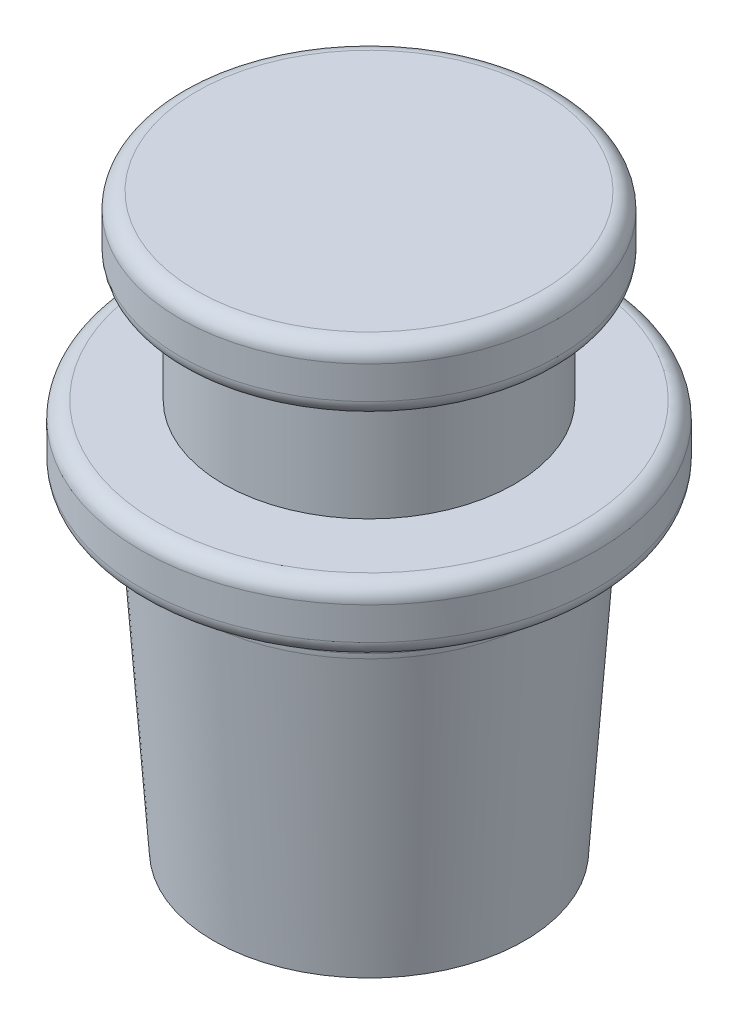
SolidWorks part; units mm, degrees
ref_plane "Front Plane" through (0, 0, 0) normal (0, 0, 1) x (1, 0, 0)
ref_plane "Top Plane" through (0, 0, 0) normal (0, 1, 0) x (1, 0, 0)
ref_plane "Right Plane" through (0, 0, 0) normal (1, 0, 0) x (0, 0, -1)
sketch "Sketch1" plane through (0, 0, 0) normal (0, 0, 1) x (1, 0, 0)
  line L0 (0, -16.038) -> (0, 17.9453) construction
  line L1 (0, 17.9453) -> (2.9, 17.9453)
  line L2 (2.9, 17.9453) -> (2.9, 16.9453)
  line L3 (2.9, 16.9453) -> (2.235, 16.9453)
  line L4 (2.235, 16.9453) -> (2.235, 15.1653)
  line L5 (2.235, 15.1653) -> (3.5, 15.1653)
  line L6 (3.5, 15.1653) -> (3.5, 14.1653)
  line L7 (3.5, 14.1653) -> (2.7, 14.1653)
  line L8 (2.7, 14.1653) -> (2.7, 9.1653)
  line L9 (2.7, 9.1653) -> (0, 9.1653)
  line L10 (0, 9.1653) -> (0, 17.9453)
  dimension "D1" = 2.9
  dimension "D2" = 1
  dimension "D3" = 2.235
  dimension "D4" = 1.78
  dimension "D5" = 3.5
  dimension "D6" = 1
  dimension "D7" = 2.7
  dimension "D8" = 5
revolve "Revolve1" add sketch "Sketch1" angle 360 about L0
fillet "Fillet2" radius 0.25 2 edges at (0, 14.1653, -3.5) (0, 15.1653, -3.5)
fillet "Fillet3" radius 0.25 2 edges at (0, 16.9453, -2.9) (0, 17.9453, -2.9)
fillet "Fillet4" radius 0.25 1 edges at (0, 14.1653, -2.7)
chamfer "Chamfer1" distance 4.5 angle 4 1 edges at (0, 9.1653, -2.7) first distance on face at (0, 13.9153, -2.7)
fillet "Fillet6" radius 1 1 edges at (0, 13.6653, -2.7)
fillet "Fillet8" radius 0.25 1 edges at (0, 16.9453, -2.235)
